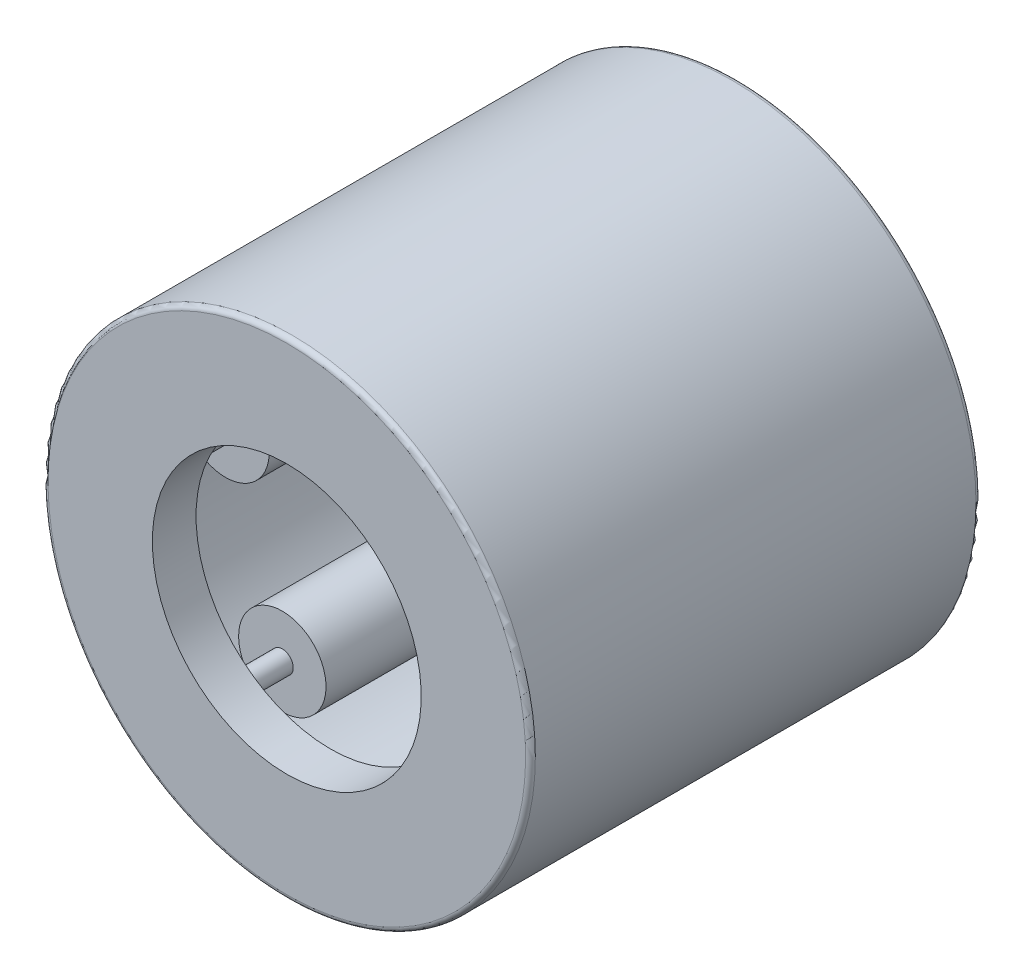
SolidWorks part; units mm, degrees
ref_plane "Front Plane" through (0, 0, 0) normal (0, 0, 1) x (1, 0, 0)
ref_plane "Top Plane" through (0, 0, 0) normal (0, 1, 0) x (1, 0, 0)
ref_plane "Right Plane" through (0, 0, 0) normal (1, 0, 0) x (0, 0, -1)
sketch "Sketch1" plane through (0, 0, 0) normal (1, 0, 0) x (0, 0, -1)
  line L0 (-3, 0) -> (3, 0) construction
  line L1 (0, 0) -> (0, 3.2465) construction
  line L2 (-3, 0) -> (-3, 3.2465) construction
  line L3 (-3, 3.2465) -> (3, 3.2465)
  line L4 (3, 3.2465) -> (3, 0) construction
  line L5 (3, 0) -> (2.4178, 0) construction
  line L6 (2.4178, 0) -> (2.4178, 2.6643) construction
  line L7 (2.4178, 2.6643) -> (-2.4178, 2.6643)
  line L8 (-2.4178, 2.6643) -> (-2.4178, 0) construction
  line L9 (-2.4178, 0) -> (-3, 0) construction
  line L10 (-3, 3.2465) -> (-3, 1.7911)
  line L11 (-3, 1.7911) -> (-2.4178, 1.7911)
  line L12 (-2.4178, 1.7911) -> (-2.4178, 2.6643)
  line L13 (2.4178, 3.2465) -> (2.4178, 2.6643) construction
  line L14 (2.4178, 2.6643) -> (2.4178, 1.7911)
  line L15 (2.4178, 1.7911) -> (3, 1.7911)
  line L16 (3, 1.7911) -> (3, 3.2465)
  line L17 (2.4178, 2.6643) -> (2.4178, 2.0822) construction
  line L18 (2.4178, 2.0822) -> (2.4178, 1.5) construction
  line L19 (2.4178, -2.6643) -> (2.4178, -2.0822) construction
  line L20 (2.4178, -3.2465) -> (2.4178, -2.6643) construction
  line L21 (3, -1.7911) -> (3, -3.2465) construction
  line L22 (2.4178, -1.7911) -> (3, -1.7911) construction
  line L23 (2.4178, -2.6643) -> (2.4178, -1.7911) construction
  line L24 (-2.4178, -1.7911) -> (-2.4178, -2.6643) construction
  line L25 (-3, -1.7911) -> (-2.4178, -1.7911) construction
  line L26 (-3, -3.2465) -> (-3, -1.7911) construction
  line L27 (2.4178, -2.6643) -> (-2.4178, -2.6643) construction
  line L28 (-3, -3.2465) -> (3, -3.2465) construction
  point P5 (0, 1.5)
  dimension "Width" = 6
  dimension "OD" = 6.493
  dimension "Shaft Dia" = 3
revolve "Revolve1" add sketch "Sketch1" angle 360 about L0
sketch "Sketch2" plane through (0, 0, 0) normal (1, 0, 0) x (0, 0, -1)
  line L0 (2.4178, 2.6643) -> (-2.4178, 2.6643) construction
  line L1 (-1.8357, 2.0822) -> (1.8357, 2.0822) construction
  line L2 (-1.8357, 2.0822) -> (-1.8357, 2.6643) construction
  line L3 (-1.8357, 2.6643) -> (1.8357, 2.6643)
  line L4 (1.8357, 2.0822) -> (1.8357, 2.6643) construction
  line L5 (2.4178, 1.7911) -> (3, 1.7911) construction
  line L6 (-2.4178, 2.0822) -> (-1.8357, 2.0822) construction
  line L7 (1.8357, 2.0822) -> (2.4178, 2.0822) construction
  line L8 (-3, 1.7911) -> (-2.4178, 1.7911) construction
  line L9 (-1.8357, 2.2277) -> (-1.8357, 1.9366) construction
  line L10 (-2.4178, 2.0822) -> (-2.4178, 1.7911) construction
  line L11 (-1.8357, 2.6643) -> (-1.8357, 2.2277)
  line L12 (1.8357, 2.6643) -> (1.8357, 2.2277)
  line L13 (1.8357, 2.2277) -> (-1.8357, 2.2277)
  line L14 (0, 2.6643) -> (0, 1.5) construction
  line L15 (-2.4178, 1.7911) -> (-2.4178, 2.6643) construction
  line L16 (-1.8357, 1.9366) -> (-2.4178, 1.9366) construction
  line L17 (0, 0) -> (3, 0) construction
  line L18 (-1.8357, -1.9366) -> (-2.4178, -1.9366) construction
  line L19 (0, -2.6643) -> (0, -1.5) construction
  line L20 (-2.4178, -2.0822) -> (-2.4178, -1.7911) construction
  line L21 (-1.8357, -2.2277) -> (-1.8357, -1.9366) construction
  line L22 (1.8357, -2.0822) -> (2.4178, -2.0822) construction
  line L23 (-2.4178, -2.0822) -> (-1.8357, -2.0822) construction
  line L24 (1.8357, -2.0822) -> (1.8357, -2.6643) construction
  line L25 (-1.8357, -2.0822) -> (-1.8357, -2.6643) construction
  line L26 (-1.8357, -2.0822) -> (1.8357, -2.0822) construction
  line L27 (1.8357, -2.2277) -> (-1.8357, -2.2277) construction
  line L28 (1.8357, -2.6643) -> (1.8357, -2.2277) construction
  line L29 (-1.8357, -2.6643) -> (-1.8357, -2.2277) construction
  line L30 (-1.8357, -2.6643) -> (1.8357, -2.6643) construction
  line L31 (3, -3.2465) -> (3, 3.2465) construction
  line L32 (2.4178, 2.6643) -> (2.4178, 1.7911) construction
  point P16 (0, 2.0822)
revolve "Revolve2" add sketch "Sketch2" angle 360 about L1
sketch "Sketch3" plane through (0, 0, 0) normal (1, 0, 0) x (0, 0, -1)
  line L0 (2.4178, 2.6643) -> (2.4178, 1.7911) construction
  line L1 (-2.4178, 2.0822) -> (2.4178, 2.0822)
  line L2 (-2.4178, 2.0822) -> (-2.4178, 2.2277)
  line L3 (-2.4178, 2.2277) -> (2.4178, 2.2277)
  line L4 (2.4178, 2.0822) -> (2.4178, 2.2277)
  line L5 (0, 0) -> (3, 0) construction
  line L6 (3, -3.2465) -> (3, 3.2465) construction
  line L7 (2.4178, -2.0822) -> (2.4178, -2.2277) construction
  line L8 (-2.4178, -2.2277) -> (2.4178, -2.2277) construction
  line L9 (-2.4178, -2.0822) -> (-2.4178, -2.2277) construction
  line L10 (-2.4178, -2.0822) -> (2.4178, -2.0822) construction
revolve "Revolve3" add sketch "Sketch3" angle 360 about L1
ref_axis "Axis1" through (0, 0, -3) along (0, 0, 1)
pattern_circular "CirPattern1" count 5 every 72 about axis through (0, 0, -3) along (0, 0, 1) of bodies 167 166
fillet "Fillet1" radius 0.0649 2 edges at (0, -3.2465, -3) (0, -3.2465, 3)
sketch "Sketch4" plane through (0, 0, 0) normal (1, 0, 0) x (0, 0, -1)
  line L0 (1.8357, 2.6643) -> (1.8357, 2.2277) construction
  line L1 (2.9351, 1.5) -> (1.8357, 1.5)
  line L2 (2.9351, 1.5) -> (2.9351, 1.7911)
  line L3 (2.9351, 1.7911) -> (1.8357, 1.7911)
  line L4 (1.8357, 1.5) -> (1.8357, 1.7911)
  line L5 (-3, 1.7911) -> (-2.4178, 1.7911) construction
  line L6 (2.9351, -3.2465) -> (2.9351, 3.2465) construction
revolve "Revolve4" [suppressed] add sketch "Sketch4" angle 360 about L0
sketch "Sketch5" plane through (0, 0, 0) normal (1, 0, 0) x (0, 0, -1)
  line L0 (-2.9351, 3.2465) -> (-2.9351, -3.2465) construction
  line L1 (-1.8357, 1.5) -> (-2.9351, 1.5)
  line L2 (-1.8357, 1.5) -> (-1.8357, 1.7911)
  line L3 (-1.8357, 1.7911) -> (-2.9351, 1.7911)
  line L4 (-2.9351, 1.5) -> (-2.9351, 1.7911)
  line L5 (-1.8357, 2.6643) -> (-1.8357, 2.2277) construction
revolve "Revolve5" [suppressed] add sketch "Sketch5" angle 360 about L0
sketch "Sketch6" plane through (0, 0, 0) normal (0, 0, 1) x (1, 0, 0)
  circle A0 centre (0, 0) radius 1.5 construction
equation "\"Rollers@CirPattern1\" = \"OD@Sketch1\"*.75"
equation "\"D1@Fillet1\" = \"OD@Sketch1\"*.01"
equation "\"Angle@CirPattern1\"= 360 / \"Rollers@CirPattern1\""
